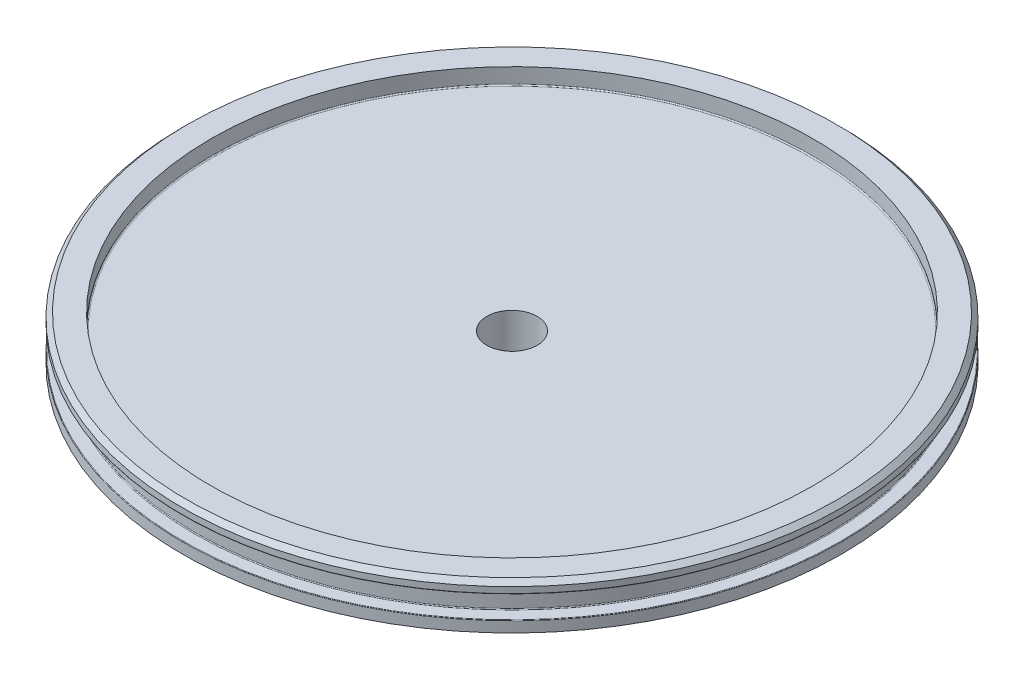
SolidWorks part; units mm, degrees
material "6061-T6 (SS)"
ref_plane "Front Plane" through (0, 0, 0) normal (0, 0, 1) x (1, 0, 0)
ref_plane "Top Plane" through (0, 0, 0) normal (0, 1, 0) x (1, 0, 0)
ref_plane "Right Plane" through (0, 0, 0) normal (1, 0, 0) x (0, 0, -1)
sketch "Sketch1" plane through (0, 0, 0) normal (0, 0, 1) x (1, 0, 0)
  line L0 (0, 48.1922) -> (0, -25.6743) construction
  line L1 (0, 0) -> (72.898, 0)
  line L2 (72.898, 0) -> (72.898, 2.4638)
  line L3 (72.898, 2.4638) -> (69.977, 2.4638)
  line L4 (69.977, 2.4638) -> (69.977, 7.4422)
  line L5 (69.977, 7.4422) -> (72.898, 7.4422)
  line L6 (72.898, 7.4422) -> (72.898, 9.906)
  line L7 (72.898, 9.906) -> (66.548, 9.906)
  line L8 (66.548, 9.906) -> (66.548, 6.35)
  line L9 (66.548, 6.35) -> (0, 6.35)
  line L10 (0, 6.35) -> (0, 0)
  dimension "D1" = 145.796
  dimension "D2" = 4.9784
  dimension "D3" = 2.921
  dimension "D4" = 9.906
  dimension "D5" = 6.35
  dimension "D6" = 6.35
revolve "Revolve1" add sketch "Sketch1" angle 360 about L0
sketch "Sketch6" plane through (0, 0, 0) normal (0, -1, 0) x (1, 0, 0)
  circle A0 centre (0, 0) radius 66.04
  dimension "D1" = 132.08
extrude "Boss-Extrude1" add sketch "Sketch6" along normal blind 2.54
hole_wizard "Pipe Tap Drill for 1/4 Tap - GN2" positions "Sketch2" profile "Sketch3" hole size "1/4" standard "ANSI Inch" end condition through all
sketch "Sketch2" plane through (0, 6.35, 0) normal (0, 1, 0) x (1, 0, 0)
  point P4 (0, 0)
  dimension "D1" = 0
sketch "Sketch3" plane through (0, 6.35, 0) normal (1, 0, 0) x (0, 0, 1)
  line L0 (0, 0) -> (0, 8.89)
  line L1 (0, 8.89) -> (5.5626, 8.89)
  line L2 (5.5626, 8.89) -> (5.5626, 0)
  line L5 (5.5626, 0) -> (0, 0)
  line L11 (0, -6.35) -> (0, 107.95) construction
  dimension "Thru Hole Dia." = 11.1252
  dimension "Thru Hole Depth" = 8.89
fillet "CNC ID Fillet" radius 0.1778 3 edges at (-69.977, 7.4422, 0) (-69.977, 2.4638, 0) (66.04, 0, 0)
fillet "CNC OD Fillet" radius 0.127 3 edges at (-72.898, 7.4422, 0) (-72.898, 2.4638, 0) (66.04, -2.54, 0)
chamfer "CNC Chamfers" distance 1.016 angle 45 1 edges at (-72.898, 9.906, 0)
fillet "CNC Bore Fillet" radius 0.254 1 edges at (-66.548, 6.35, 0)
